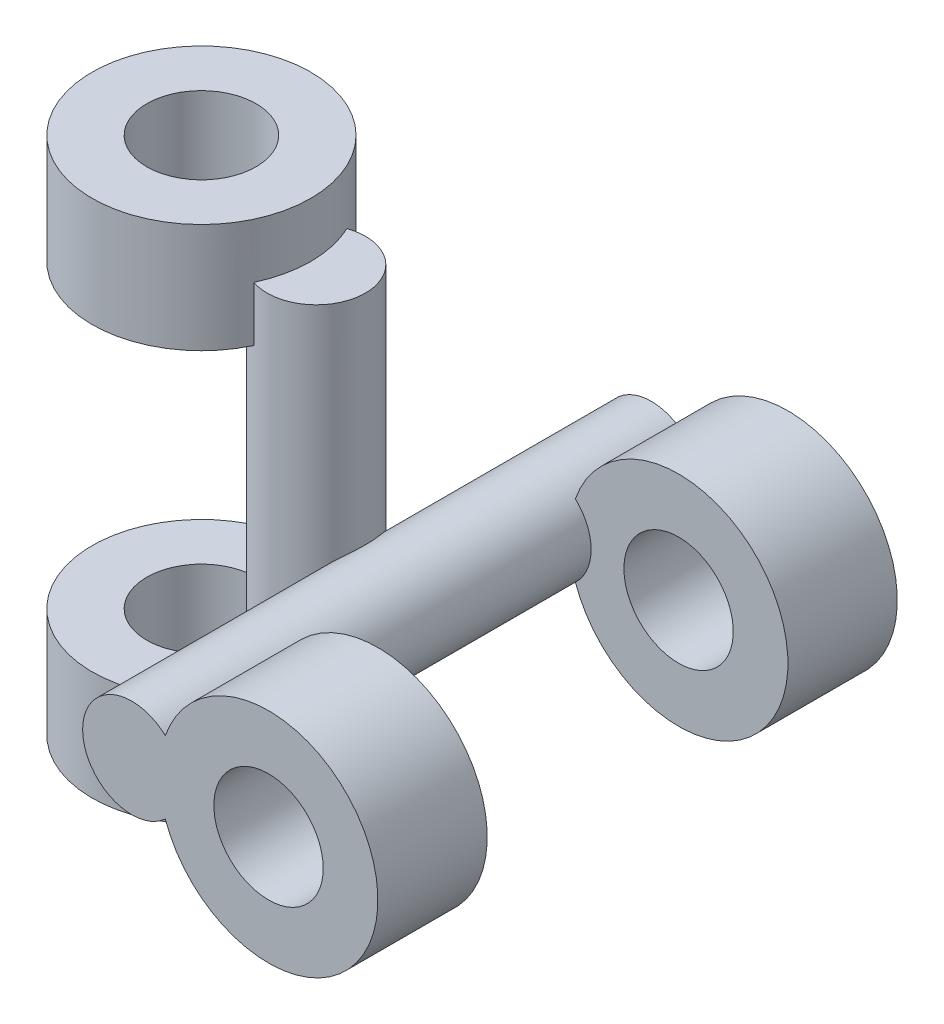
SolidWorks part; units mm, degrees
ref_plane "前视基准面" through (0, 0, 0) normal (0, 0, 1) x (1, 0, 0)
ref_plane "上视基准面" through (0, 0, 0) normal (0, 1, 0) x (1, 0, 0)
ref_plane "右视基准面" through (0, 0, 0) normal (1, 0, 0) x (0, 0, -1)
other "Configuration Table"
sketch "草图1" plane through (0, 0, 0) normal (0, 1, 0) x (1, 0, 0)
  circle A0 centre (0, 0) radius 1
extrude "拉伸-薄壁1" add sketch "草图1" along normal blind 2 thin thin type one direction wall 1
sketch "草图2" plane through (0, 0, 0) normal (0, -1, 0) x (1, 0, 0)
  line L0 (0, 0) -> (2.1, 0) construction
  circle A0 centre (2.1, 0) radius 0.9
  dimension "D1" = 1.8
  dimension "D2" = 2.1
extrude "凸台-拉伸1" add sketch "草图2" along normal blind 7.5 and the other way blind 1
sketch "草图3" plane through (0, -7.5, 0) normal (0, -1, 0) x (1, 0, 0)
  circle A0 centre (0, 0) radius 2 construction
  circle A3 centre (0, 0) radius 1 construction
  circle A4 centre (0, 0) radius 2
  circle A5 centre (0, 0) radius 1
extrude "凸台-拉伸2" add sketch "草图3" against normal blind 2
sketch "草图4" plane through (0, 0, 0) normal (0, 0, 1) x (1, 0, 0)
  line L0 (2.4048, -7.5) -> (2.4048, 0) construction
  line L1 (1.8095, -7.5) -> (3, -7.5) construction
  circle A0 centre (2.4048, -3.75) radius 0.5
ref_plane "基准面1" through (1.8773, 0, 0) normal (1, 0, 0) x (0, 0, -1)
sketch "草图7" plane through (1.8773, 0, 0) normal (1, 0, 0) x (0, 0, -1)
  line L0 (0, -3.25) -> (0, -4.25) construction
  circle A0 centre (0, -3.75) radius 0.5
extrude "凸台-拉伸4" add sketch "草图7" along normal blind 2
sketch "草图11" plane through (0, 0, 0) normal (0, 0, 1) x (1, 0, 0)
  line L1 (3.8773, -4.25) -> (3.8773, -3.25) construction
  line L2 (3, -4.25) -> (3.8773, -4.25) construction
  circle A0 centre (3.4773, -3.75) radius 0.9
  dimension "D1" = 0.4
  dimension "D3" = 1.8
  dimension "D2" = 0.5
extrude "凸台-拉伸7" add sketch "草图11" along normal blind 2.75 and the other way blind 2.75
sketch "草图12" plane through (0, 0, 2.75) normal (0, 0, 1) x (1, 0, 0)
  line L0 (3.4773, -3.75) -> (5.9773, -3.75) construction
  circle A0 centre (5.9773, -3.75) radius 2
  circle A1 centre (3.4773, -3.75) radius 0.9 construction
  dimension "D1" = 2.5
extrude "拉伸-薄壁5" add sketch "草图12" along normal blind 2 thin thin type one direction reverse wall 1
sketch "草图13" plane through (0, 0, -2.75) normal (0, 0, -1) x (-1, 0, 0)
  line L0 (-3.4773, -3.75) -> (-5.9773, -3.75) construction
  circle A0 centre (-5.9773, -3.75) radius 2
  circle A3 centre (-3.4773, -3.75) radius 0.9 construction
  dimension "D1" = 2.5
extrude "拉伸-薄壁6" add sketch "草图13" along normal blind 2 thin thin type one direction reverse wall 1
sketch "草图15" plane through (0, 0, -2.75) normal (0, 0, -1) x (-1, 0, 0)
  arc A0 (-4.0893, -4.4099) -> (-4.0893, -3.0901) centre (-3.4773, -3.75) ccw construction
  arc A1 (-4.0893, -4.4099) -> (-4.0893, -3.0901) centre (-3.4773, -3.75) ccw
  circle A2 centre (-3.4773, -3.75) radius 0.9
extrude "凸台-拉伸8" add sketch "草图15" along normal blind 2 contours A2
sketch "草图16" plane through (0, 0, 2.75) normal (0, 0, 1) x (1, 0, 0)
  arc A0 (4.0893, -3.0901) -> (4.0893, -4.4099) centre (3.4773, -3.75) ccw construction
  arc A1 (4.0893, -3.0901) -> (4.0893, -4.4099) centre (3.4773, -3.75) ccw
  circle A2 centre (3.4773, -3.75) radius 0.9
extrude "凸台-拉伸9" add sketch "草图16" along normal blind 2 contours A2
